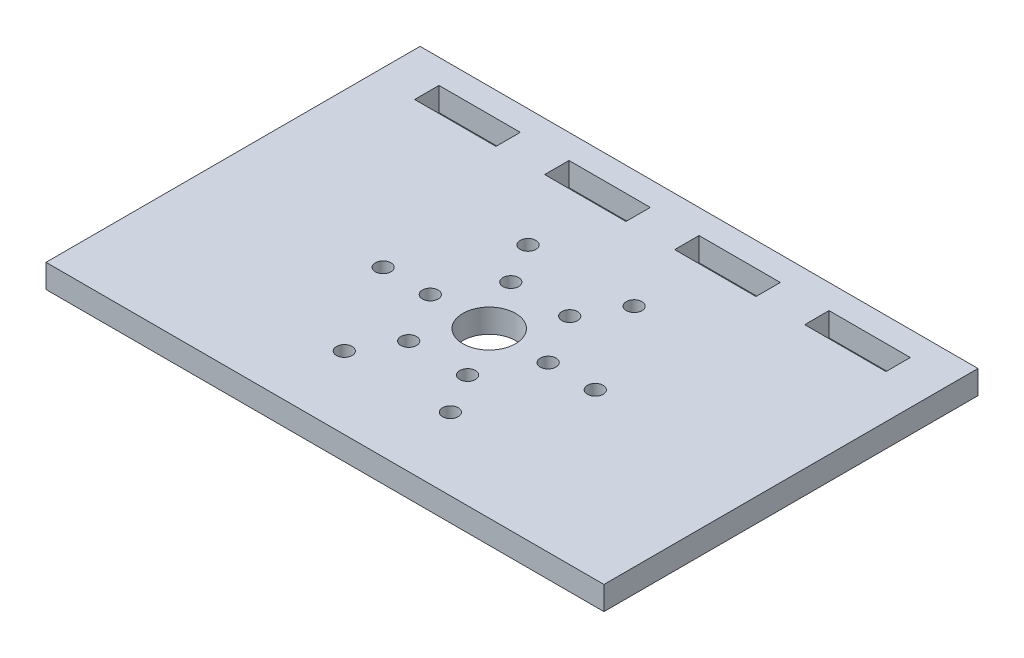
SolidWorks part; units mm, degrees
ref_plane "Front Plane" through (0, 0, 0) normal (0, 0, 1) x (1, 0, 0)
ref_plane "Top Plane" through (0, 0, 0) normal (0, 1, 0) x (1, 0, 0)
ref_plane "Right Plane" through (0, 0, 0) normal (1, 0, 0) x (0, 0, -1)
sketch "Sketch2" plane through (0, 0, 0) normal (0, 1, 0) x (1, 0, 0)
  line L0 (0, 0) -> (71, 0)
  line L1 (71, 0) -> (71, 47.6)
  line L2 (71, 47.6) -> (0, 47.6)
  line L3 (0, 47.6) -> (0, 0)
  line L9 (0, 44.5) -> (5.512, 44.5)
  line L11 (5.512, 44.5) -> (15.856, 44.5)
  line L12 (5.512, 44.5) -> (5.512, 41.4)
  line L13 (5.512, 41.4) -> (15.856, 41.4)
  line L14 (15.856, 41.4) -> (15.856, 44.5)
  line L16 (22.056, 44.5) -> (32.4, 44.5)
  line L17 (22.056, 44.5) -> (22.056, 41.4)
  line L18 (22.056, 41.4) -> (32.4, 41.4)
  line L19 (32.4, 41.4) -> (32.4, 44.5)
  line L20 (38.6, 44.5) -> (48.944, 44.5)
  line L21 (48.944, 44.5) -> (48.944, 41.4)
  line L22 (48.944, 41.4) -> (38.6, 41.4)
  line L23 (38.6, 41.4) -> (38.6, 44.5)
  line L24 (55.144, 44.5) -> (65.488, 44.5)
  line L25 (65.488, 44.5) -> (65.488, 41.4)
  line L26 (65.488, 41.4) -> (55.144, 41.4)
  line L27 (55.144, 41.4) -> (55.144, 44.5)
  circle A0 centre (35.5, 20.9) radius 3.35
  circle A1 centre (43, 20.9) radius 1
  circle A2 centre (49, 20.9) radius 1
  circle A3 centre (39.25, 14.4048) radius 1
  circle A4 centre (42.25, 9.2087) radius 1
  circle A5 centre (31.75, 14.4048) radius 1
  circle A6 centre (28.75, 9.2087) radius 1
  circle A7 centre (28, 20.9) radius 1
  circle A8 centre (22, 20.9) radius 1
  circle A9 centre (31.75, 27.3952) radius 1
  circle A10 centre (28.75, 32.5913) radius 1
  circle A11 centre (39.25, 27.3952) radius 1
  circle A12 centre (42.25, 32.5913) radius 1
  point P34 (35.5, 20.9)
  dimension "D3" = 20.9
  dimension "D4" = 2
  dimension "D5" = 2
  dimension "D6" = 6.7
  dimension "D7" = 7.5
  dimension "D8" = 6
  dimension "D1" = 71
  dimension "D2" = 47.6
  dimension "D10" = 5.512
  dimension "D11" = 3.1
  dimension "D12" = 10.344
  dimension "D13" = 3.1
  dimension "D14" = 10.344
  dimension "D15" = 6.2
  dimension "D16" = 6.2
  dimension "D17" = 10.344
  dimension "D18" = 10.344
  dimension "D19" = 6.2
  dimension "D20" = 5.512
  dimension "D9" = 6
extrude "Boss-Extrude1" add sketch "Sketch2" along normal blind 3 contours L14 L13 L12 L3 L0 L1 L2 L11 A12 A11 A10 A9 A8 A7 A6 A5 A4 A3 A2 A1 A0 L19 L18 L17 L16 L22 L23 L20 L21 L26 L27 L24 region at (0.8548, 0, -22.25)
